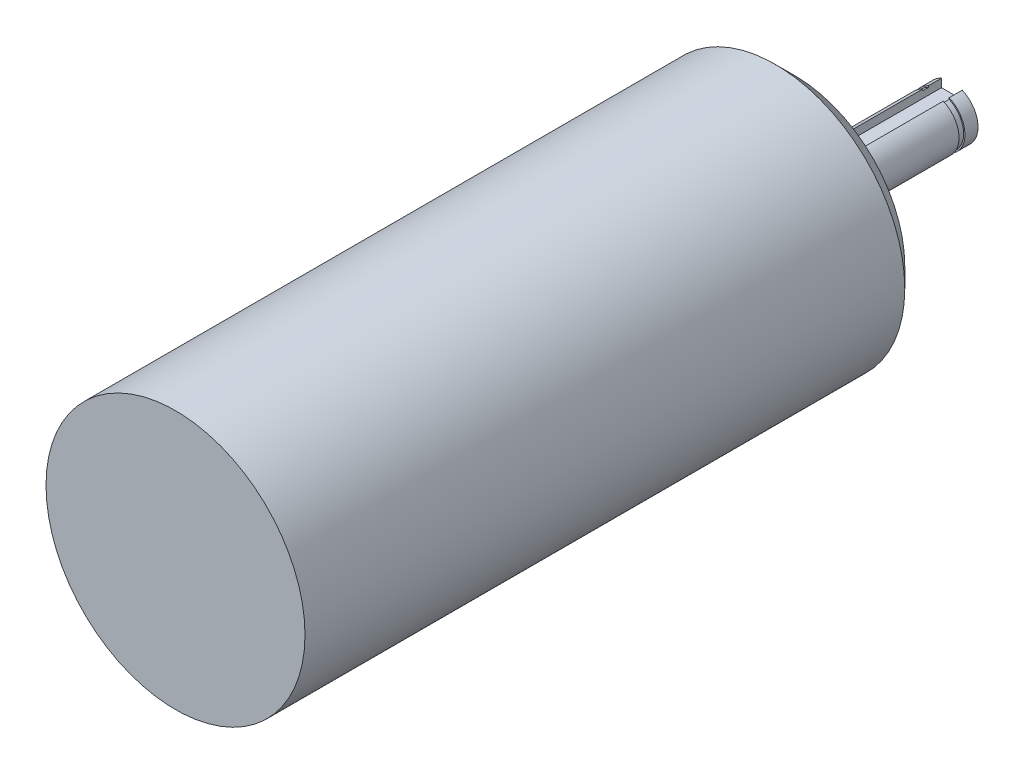
SolidWorks part; units mm, degrees
ref_plane "Front Plane" through (0, 0, 0) normal (0, 0, 1) x (1, 0, 0)
ref_plane "Top Plane" through (0, 0, 0) normal (0, 1, 0) x (1, 0, 0)
ref_plane "Right Plane" through (0, 0, 0) normal (1, 0, 0) x (0, 0, -1)
sketch "Sketch1" plane through (0, 0, 0) normal (0, 0, 1) x (1, 0, 0)
  circle A0 centre (0, 0) radius 19.8
  dimension "D1" = 39.6
extrude "Boss-Extrude1" add sketch "Sketch1" along normal blind 94.7
sketch "face mounting holes" plane through (0, 0, 0) normal (0, 0, -1) x (-1, 0, 0)
  point P0 (0, 12.5)
  point P4 (12.5, 0)
  point P5 (0, -12.5)
  point P6 (-12.5, 0)
  point P7 (0, 0)
  dimension "D2" = 25
  dimension "D1" = 4
hole_wizard "M4x0.7 Tapped Hole1" positions "Sketch3" profile "Sketch5" tap size "M4x0.7" standard "ANSI Metric"
sketch "Sketch3" plane through (0, 0, 0) normal (0, 0, -1) x (-1, 0, 0)
  point P0 (0, 12.5)
  point P3 (-12.5, 0)
  point P6 (0, -12.5)
  point P9 (12.5, 0)
sketch "Sketch5" plane through (0, 12.5, 0) normal (1, 0, 0) x (0, 1, 0)
  line L0 (0, 0) -> (0, 4.9914)
  line L1 (0, 4.9914) -> (1.65, 4)
  line L2 (1.65, 4) -> (1.65, 0.375)
  line L3 (1.65, 0.375) -> (2.025, 0)
  line L5 (2.025, 0) -> (0, 0)
  line L6 (-1.65, 0.375) -> (-2.025, 0) construction
  line L10 (0, 4.9914) -> (-1.65, 4) construction
  line L11 (0, -6.35) -> (0, 107.95) construction
  dimension "Tap Drill Dia." = 3.3
  dimension "Tap Drill Depth" = 4
  dimension "Near C'Sink Dia." = 4.05
  dimension "Near C'Sink Angle" = 90
  dimension "Drill Angle" = 118
cosmetic thread "Hole Thread1" parameters "D1"=4, "D2"=4
cosmetic thread "Hole Thread2" parameters "D1"=4, "D2"=4
cosmetic thread "Hole Thread3" parameters "D1"=4, "D2"=4
cosmetic thread "Hole Thread4" parameters "D1"=4, "D2"=4
sketch "Sketch6" plane through (0, 0, 0) normal (0, 0, -1) x (-1, 0, 0)
  circle A0 centre (0, 0) radius 4
  dimension "D1" = 8
extrude "Boss-Extrude2" add sketch "Sketch6" along normal blind 24
chamfer "Chamfer1" distance 3 angle 45 1 edges at (19.8, 0, 0)
sketch "Sketch7" plane through (0, 0, -24) normal (0, 0, -1) x (-1, 0, 0)
  line L1 (-1.5875, 2.4125) -> (1.5875, 2.4125)
  line L2 (-1.5875, 2.4125) -> (-1.5875, 5.5875)
  line L3 (-1.5875, 5.5875) -> (1.5875, 5.5875)
  line L4 (1.5875, 2.4125) -> (1.5875, 5.5875)
  line L5 (-1.5875, 2.4125) -> (1.5875, 5.5875) construction
  line L6 (-1.5875, 5.5875) -> (1.5875, 2.4125) construction
  circle A0 centre (0, 0) radius 4 construction
  point P0 (0, 4)
  dimension "D1" = 3.175
  dimension "D2" = 3.175
extrude "Cut-Extrude1" cut sketch "Sketch7" against normal blind 19
ref_plane "Plane1" through (0, 0, -22) normal (0, 0, -1) x (-1, 0, 0)
sketch "Sketch8" plane through (0, 0, -22) normal (0, 0, -1) x (-1, 0, 0)
  circle A0 centre (0, 0) radius 3.8
  circle A1 centre (0, 0) radius 4
  arc A2 (-1.5875, 3.6715) -> (1.5875, 3.6715) centre (0, 0) ccw construction
  dimension "D1" = 7.6
extrude "Cut-Extrude2" cut sketch "Sketch8" against normal blind 0.9
equation "\"D1@Sketch7\"=0.125in"
equation "\"D2@Sketch7\"=0.125in"
